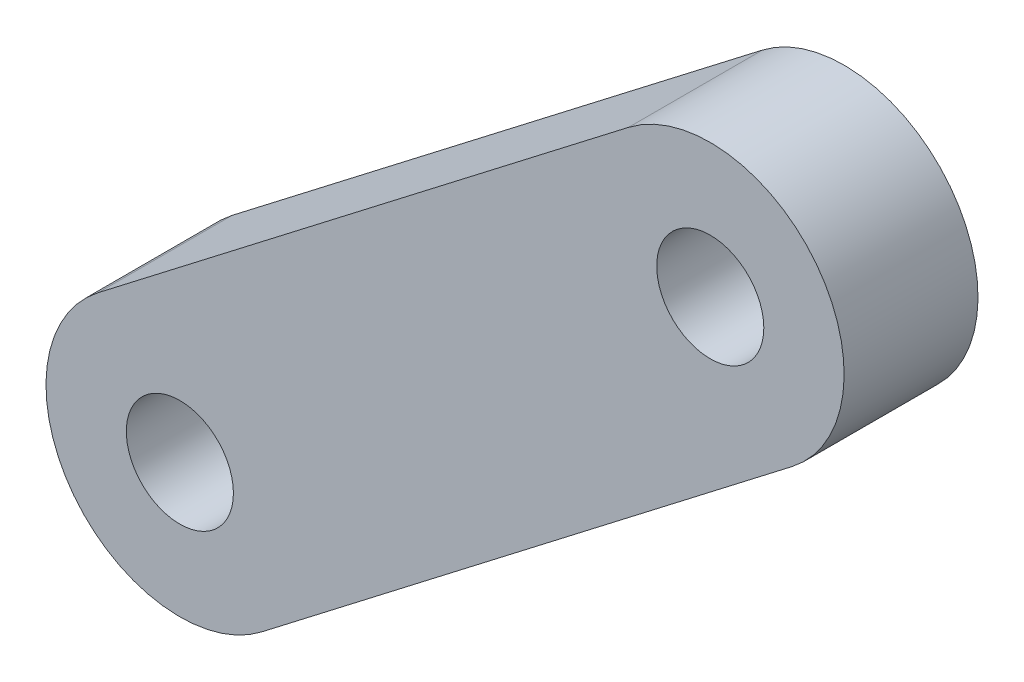
SolidWorks part; units mm, degrees
ref_plane "Front Plane" through (0, 0, 0) normal (0, 0, 1) x (1, 0, 0)
ref_plane "Top Plane" through (0, 0, 0) normal (0, 1, 0) x (1, 0, 0)
ref_plane "Right Plane" through (0, 0, 0) normal (1, 0, 0) x (0, 0, -1)
sketch "Sketch1" plane through (0, 0, 0) normal (0, 0, 1) x (0.9998, -0.022, 0)
  line L0 (-41.8829, 111.4723) -> (-17.0715, 91.626) construction
  line L1 (-1.7639, 79.3817) -> (-1.7639, 99.3817) construction
  line L2 (-1.7639, 99.3817) -> (-51.7712, 99.3817) construction
  line L3 (-46.2352, 83.6971) -> (-26.7675, 99.3817) construction
  line L4 (-46.2352, 83.6971) -> (-49.3722, 87.5906) construction
  line L5 (-49.3722, 87.5906) -> (-43.0983, 79.8035) construction
  line L6 (-49.3722, 87.5906) -> (-29.9044, 103.2753)
  line L7 (-43.0983, 79.8035) -> (-23.6306, 95.4882)
  line L8 (-29.9044, 103.2753) -> (-23.6306, 95.4882) construction
  circle A0 centre (-1.7639, 79.3817) radius 2.5 construction
  circle A1 centre (-1.7639, 79.3817) radius 2.5 construction
  circle A3 centre (-26.7675, 99.3817) radius 2
  arc A4 (-22.8629, 96.2585) -> (-30.6611, 96.2448) centre (-26.7675, 99.3817) ccw
  circle A5 centre (-46.2352, 83.6971) radius 2 construction
  circle A6 centre (-46.2352, 83.6971) radius 2
  arc A7 (-49.3722, 87.5906) -> (-43.0983, 79.8035) centre (-46.2352, 83.6971) ccw
  arc A8 (-23.6306, 95.4882) -> (-29.9044, 103.2753) centre (-26.7675, 99.3817) ccw
  point P18 (-26.7675, 99.3817)
  dimension "D1" = 5
  dimension "D2" = 5
  dimension "D4" = 4
  dimension "D5" = 4
  dimension "D6" = 10
  dimension "D3" = 20
  dimension "D7" = 25
extrude "Boss-Extrude1" add sketch "Sketch1" along normal blind 5 contours L7 A8 L6 A7 A3 A6 region at (-34.4759, 92.3213, 0)
sketch "Sketch2" plane through (0, 0, 0) normal (0, 0, -1) x (-1, 0, 0)
  circle A0 centre (44.3801, 84.6953) radius 2
